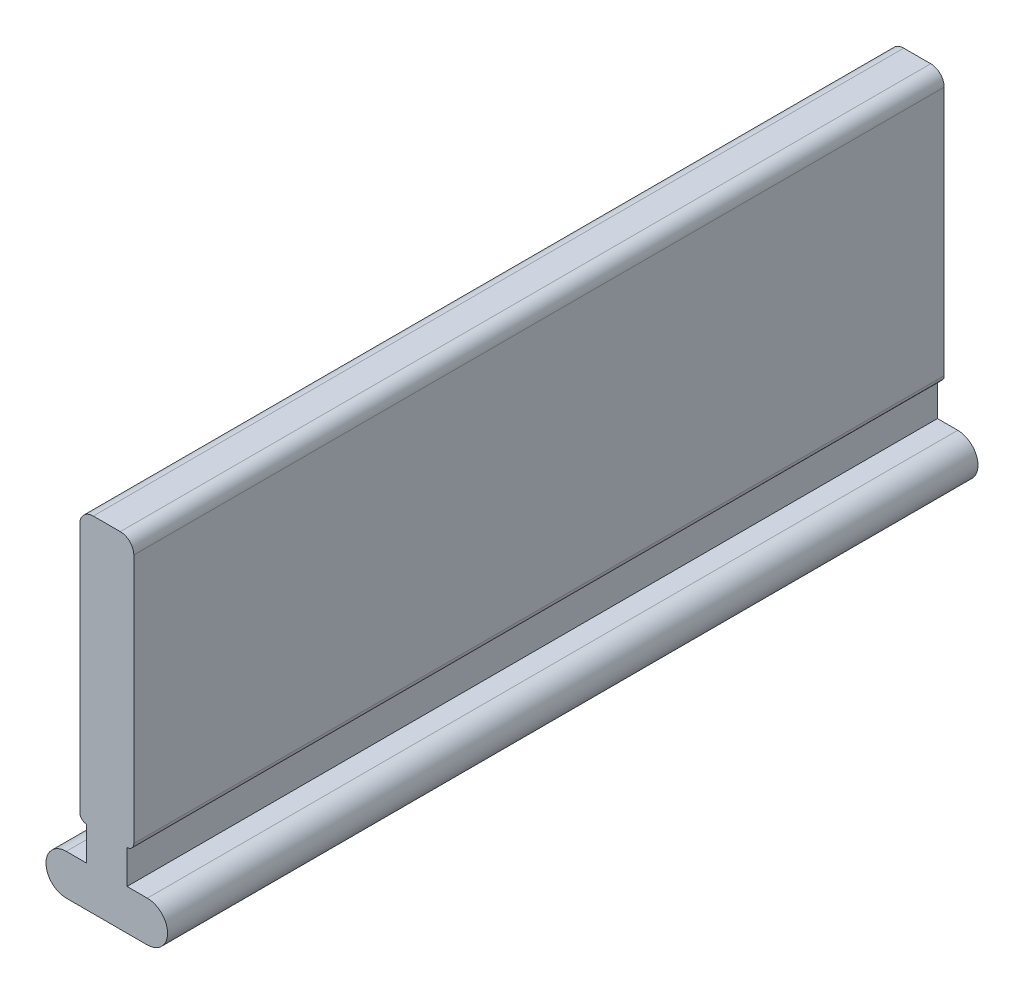
SolidWorks part; units mm, degrees
ref_plane "Front Plane" through (0, 0, 0) normal (0, 0, 1) x (1, 0, 0)
ref_plane "Top Plane" through (0, 0, 0) normal (0, 1, 0) x (1, 0, 0)
ref_plane "Right Plane" through (0, 0, 0) normal (1, 0, 0) x (0, 0, -1)
sketch "Sketch1" plane through (0, 0, 0) normal (0, 0, 1) x (1, 0, 0)
  line L0 (-2, 3) -> (-2, 23)
  line L1 (-6, 3) -> (-2, 3)
  line L2 (-6, 3) -> (-6, -3)
  line L3 (-6, -3) -> (6, -3)
  line L4 (6, 3) -> (6, -3)
  line L5 (-6, 3) -> (6, -3) construction
  line L6 (-6, -3) -> (6, 3) construction
  line L7 (-2, 23) -> (2, 23)
  line L8 (2, 23) -> (2, 3)
  line L11 (2, 3) -> (6, 3)
  point P0 (0, 0)
  dimension "D1" = 12
  dimension "D2" = 6
  dimension "D3" = 4
  dimension "D4" = 2
  dimension "D5" = 20
extrude "Boss-Extrude1" add sketch "Sketch1" along normal blind 60
sketch "Sketch2" plane through (0, 0, 60) normal (0, 0, 1) x (1, 0, 0)
  line L0 (6, -3) -> (6, 3) construction
  line L1 (-6, -3) -> (6, -3)
  line L2 (-6, -3) -> (-6, 3)
  line L3 (-6, 3) -> (-1.5, 3)
  line L4 (6, -3) -> (6, 3)
  line L5 (-3, -1) -> (3, -1) construction
  line L6 (-3, 0.5) -> (-1.5, 0.5)
  line L7 (-3, -2.5) -> (3, -2.5)
  line L8 (0, -1) -> (0, 2.5) construction
  line L10 (-1.5, 3) -> (-1.5, 0.5)
  line L12 (1.5, 3) -> (1.5, 0.5)
  line L13 (1.5, 3) -> (6, 3)
  line L14 (1.5, 0.5) -> (3, 0.5)
  arc A0 (-3, 0.5) -> (-3, -2.5) centre (-3, -1) ccw
  arc A1 (3, -2.5) -> (3, 0.5) centre (3, -1) ccw
  point P9 (0, -1)
  dimension "D1" = 6
  dimension "D2" = 4
  dimension "D3" = 3
  dimension "D4" = 6
  dimension "D5" = 6
  dimension "D6" = 1.5
  dimension "D7" = 1.5
  dimension "D8" = 3
extrude "Cut-Extrude1" cut sketch "Sketch2" against normal up to surface (60 mm away) up to face at (0, 6.5, 0)
fillet "Fillet19" radius 0.5 1 edges at (-2, 3, 30) type face fillet first side face at (-2, 13, 30) second side face at (-1.75, 3, 30)
fillet "Fillet20" radius 0.5 1 edges at (2, 3, 30) type face fillet first side face at (2, 13, 30) second side face at (1.75, 3, 30)
fillet "Fillet22" radius 1 2 edges at (-2, 23, 30) (2, 23, 30)
